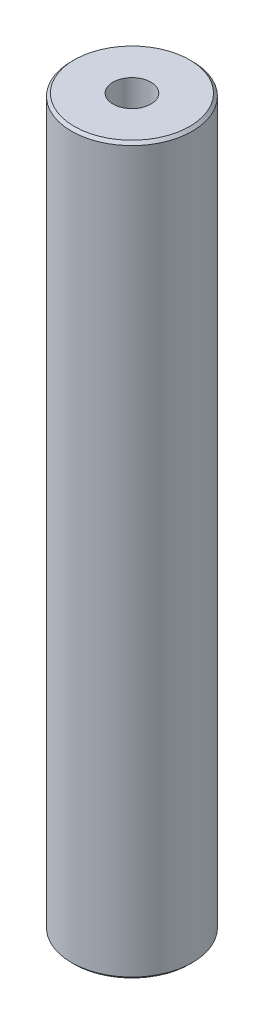
SolidWorks part; units mm, degrees
ref_plane "Front Plane" through (0, 0, 0) normal (0, 0, 1) x (1, 0, 0)
ref_plane "Top Plane" through (0, 0, 0) normal (0, 1, 0) x (1, 0, 0)
ref_plane "Right Plane" through (0, 0, 0) normal (1, 0, 0) x (0, 0, -1)
sketch "Sketch1" plane through (0, 0, 0) normal (0, 1, 0) x (1, 0, 0)
  circle A0 centre (0, 0) radius 50
  dimension "SHAFT_OD" = 100
extrude "Boss-Extrude1" add sketch "Sketch1" along normal blind 600
sketch "Sketch2" plane through (0, 0, 0) normal (0, 1, 0) x (1, 0, 0)
  circle A0 centre (0, 0) radius 15.7109
  dimension "BORE_D" = 31.4218
extrude "Cut-Extrude1" cut sketch "Sketch2" along normal through all
chamfer "Chamfer1" distance 2.2747 angle 45 2 edges at (0, 600, 50) (0, 0, 50)
